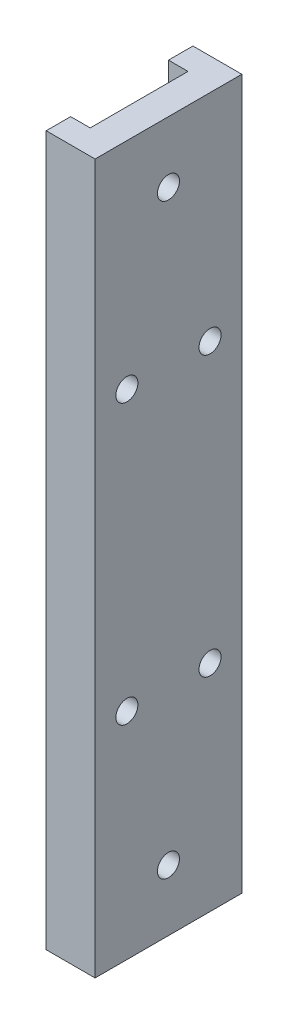
SolidWorks part; units mm, degrees
ref_plane "Front Plane" through (0, 0, 0) normal (0, 0, 1) x (1, 0, 0)
ref_plane "Top Plane" through (0, 0, 0) normal (0, 1, 0) x (1, 0, 0)
ref_plane "Right Plane" through (0, 0, 0) normal (1, 0, 0) x (0, 0, -1)
ref_plane "Plane1" through (0, 260, 0) normal (0, -1, 0) x (-1, 0, 0)
sketch "Sketch1" plane through (0, 260, 0) normal (0, -1, 0) x (-1, 0, 0)
  line L0 (71.5, -127.5) -> (61.5, -127.5)
  line L1 (61.5, -127.5) -> (61.5, -97.5)
  line L2 (61.5, -97.5) -> (71.5, -97.5)
  line L3 (71.5, -97.5) -> (71.5, -102.5)
  line L4 (71.5, -102.5) -> (67.5, -102.5)
  line L5 (67.5, -102.5) -> (67.5, -122.5)
  line L6 (67.5, -122.5) -> (71.5, -122.5)
  line L7 (71.5, -122.5) -> (71.5, -127.5)
  line L8 (68.9986, -122.5) -> (74.3631, -122.5) construction
  line L9 (68.9986, -102.5) -> (74.3631, -102.5) construction
  line L10 (67.5, -115.6369) -> (67.5, -121.0014) construction
  dimension "D1" = 5
  dimension "D2" = 10
  dimension "D3" = 6
extrude "Boss-Extrude1" add sketch "Sketch1" along normal blind 145
sketch "Sketch5" plane through (-61.5, 0, 0) normal (1, 0, 0) x (0, 0, -1)
  line L0 (-97.5, 260) -> (-127.5, 260) construction
  line L1 (-121, 159) -> (-104, 159) construction
  line L2 (-121, 159) -> (-121, 216) construction
  line L3 (-121, 216) -> (-104, 216) construction
  line L4 (-104, 159) -> (-104, 216) construction
  line L5 (-121, 159) -> (-104, 216) construction
  line L6 (-121, 216) -> (-104, 159) construction
  line L7 (-97.5, 115) -> (-97.5, 260) construction
  point P0 (-112.5, 187.5)
  point P8 (-112.5, 260)
  point P11 (-97.5, 187.5)
  dimension "D1" = 17
  dimension "D2" = 57
hole_wizard "M4 Clearance Hole1" positions "Sketch2" profile "Sketch4" hole size "M4" standard "ISO" end condition through all
sketch "Sketch2" plane through (-61.5, 0, 0) normal (1, 0, 0) x (0, 0, -1)
  line L0 (-112.5, 247.5) -> (-112.5, 127.5) construction
  line L2 (-97.5, 260) -> (-127.5, 260) construction
  line L4 (-112.5, 247.5) -> (-112.5, 260) construction
  line L7 (-112.5, 127.5) -> (-112.5, 115) construction
  line L8 (-97.5, 115) -> (-127.5, 115) construction
  point P1 (-112.5, 247.5)
  point P2 (-112.5, 127.5)
  point P7 (-112.5, 260)
  dimension "D1" = 120
sketch "Sketch4" plane through (-61.5, 247.5, 112.5) normal (0, 1, 0) x (0, 0, -1)
  line L0 (0, 0) -> (0, 10)
  line L1 (0, 10) -> (2.25, 10)
  line L2 (2.25, 10) -> (2.25, 0)
  line L5 (2.25, 0) -> (0, 0)
  line L11 (0, -6.35) -> (0, 107.95) construction
  dimension "Thru Hole Dia." = 4.5
  dimension "Thru Hole Depth" = 10
hole_wizard "Hole1" positions "Sketch6" profile "Sketch7" legacy
sketch "Sketch6" plane through (-61.5, 0, 0) normal (1, 0, 0) x (0, 0, -1)
  point P0 (-104, 216)
  point P3 (-121, 216)
  point P6 (-104, 159)
  point P9 (-121, 159)
sketch "Sketch7" plane through (-61.5, 216, 104) normal (0, 1, 0) x (0, 0, -1)
  line L0 (0, 0) -> (0, 6)
  line L1 (0, 6) -> (2.25, 6)
  line L2 (2.25, 6) -> (2.25, 0)
  line L3 (2.25, 0) -> (0, 0)
  line L4 (0, 110) -> (0, -10) construction
  dimension "Diameter" = 4.5
  dimension "Depth" = 6
